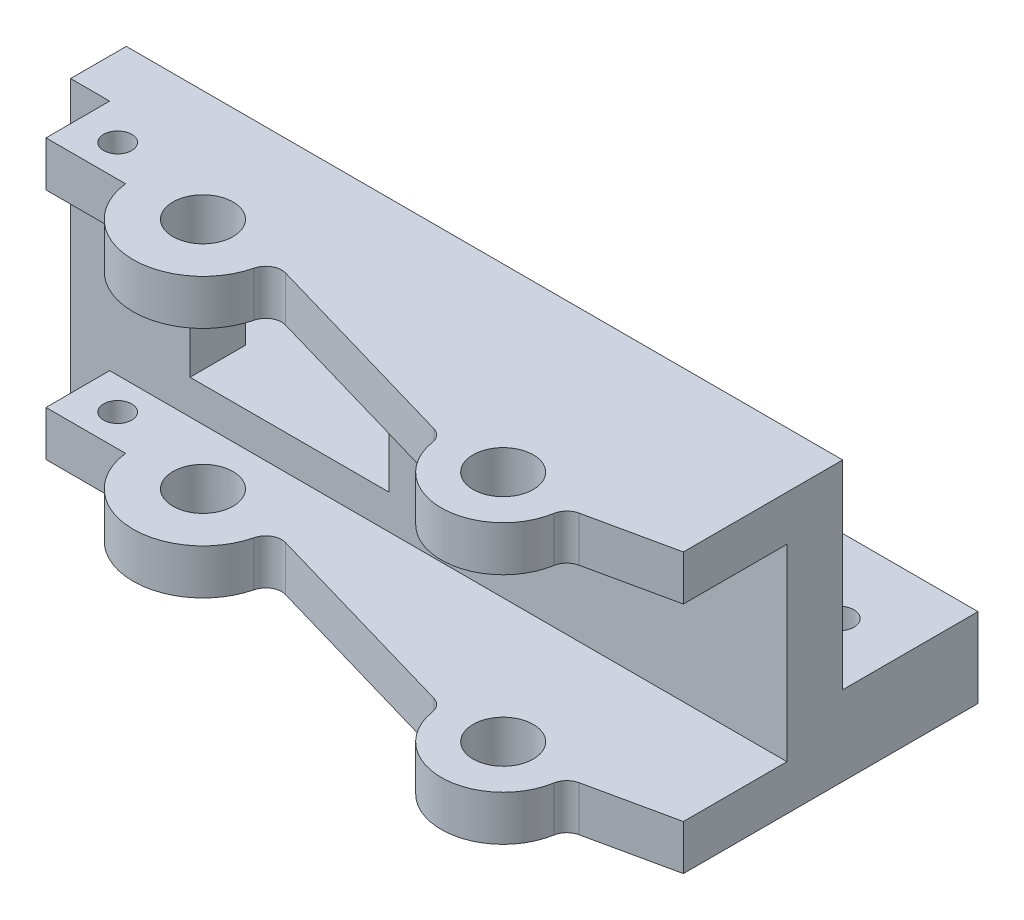
SolidWorks part; units mm, degrees
ref_plane "Front Plane" through (0, 0, 0) normal (0, 0, 1) x (1, 0, 0)
ref_plane "Top Plane" through (0, 0, 0) normal (0, 1, 0) x (1, 0, 0)
ref_plane "Right Plane" through (0, 0, 0) normal (1, 0, 0) x (0, 0, -1)
sketch "Sketch1" plane through (0, 0, 0) normal (0, 0, 1) x (1, 0, 0)
  line L1 (57.15, -22.225) -> (-57.15, -22.225)
  line L2 (57.15, -22.225) -> (57.15, 22.225)
  line L3 (57.15, 22.225) -> (-57.15, 22.225)
  line L4 (-57.15, -22.225) -> (-57.15, 22.225)
  line L5 (57.15, -22.225) -> (-57.15, 22.225) construction
  line L6 (57.15, 22.225) -> (-57.15, -22.225) construction
  point P0 (0, 0)
  dimension "D1" = 44.45
  dimension "D2" = 114.3
extrude "Boss-Extrude1" add sketch "Sketch1" along normal blind 62.23
sketch "Sketch2" plane through (0, 0, 62.23) normal (0, 0, 1) x (1, 0, 0)
  line L0 (-57.15, 22.225) -> (-57.15, -22.225) construction
  line L1 (57.15, -15.025) -> (-57.15, -15.025)
  line L2 (57.15, -15.025) -> (57.15, 15.025)
  line L3 (57.15, 15.025) -> (-57.15, 15.025)
  line L4 (-57.15, -15.025) -> (-57.15, 15.025)
  line L5 (57.15, -15.025) -> (-57.15, 15.025) construction
  line L6 (57.15, 15.025) -> (-57.15, -15.025) construction
  line L7 (57.15, 22.225) -> (-57.15, 22.225) construction
  point P0 (0, 0)
  dimension "D1" = 7.2
extrude "Cut-Extrude2" cut sketch "Sketch2" against normal blind 31.75
sketch "Sketch3" plane through (0, 0, 0) normal (0, 0, -1) x (-1, 0, 0)
  line L0 (-57.15, -22.225) -> (-57.15, 22.225) construction
  line L1 (57.15, 22.225) -> (-57.15, 22.225)
  line L2 (57.15, 22.225) -> (57.15, -9.525)
  line L3 (57.15, -9.525) -> (-57.15, -9.525)
  line L4 (-57.15, 22.225) -> (-57.15, -9.525)
  line L5 (57.15, -22.225) -> (-57.15, -22.225) construction
  dimension "D1" = 12.7
extrude "Cut-Extrude3" cut sketch "Sketch3" against normal blind 21.59
sketch "Sketch5" plane through (0, -22.225, 0) normal (0, -1, 0) x (1, 0, 0)
  line L0 (-3.81, 12.06) -> (46.99, 12.06) construction
  line L1 (57.15, 21.59) -> (-57.15, 21.59) construction
  line L2 (57.15, 62.23) -> (57.15, 0) construction
  circle A0 centre (-3.81, 12.06) radius 2.415
  circle A1 centre (46.99, 12.06) radius 2.415
  dimension "D3" = 4.83
  dimension "D4" = 10.16
  dimension "D1" = 9.53
  dimension "D2" = 50.8
extrude "Cut-Extrude4" cut sketch "Sketch5" against normal blind 25.4
sketch "Sketch7" plane through (0, -22.225, 0) normal (0, -1, 0) x (1, 0, 0)
  line L0 (57.15, 62.23) -> (57.15, 0) construction
  line L1 (-57.15, 0) -> (57.15, 0) construction
  circle A0 centre (31.75, 50.36) radius 4.8
  circle A1 centre (-27.14, 39.37) radius 4.8
  dimension "D1" = 9.6
  dimension "D2" = 25.4
  dimension "D3" = 39.37
  dimension "D4" = 9.6
  dimension "D5" = 58.89
  dimension "D6" = 10.99
extrude "Cut-Extrude6" cut sketch "Sketch7" against normal up to surface (44.45 mm away) up to face at (0, 22.225, 41.91)
sketch "Sketch9" plane through (0, 0, 30.48) normal (0, 0, 1) x (1, 0, 0)
  line L5 (57.15, 15.025) -> (-57.15, 15.025) construction
  line L6 (-38.1, 15.025) -> (-6.35, 15.025)
  line L7 (-38.1, 15.025) -> (-38.1, -15.025)
  line L8 (-38.1, -15.025) -> (-6.35, -15.025)
  line L9 (-6.35, 15.025) -> (-6.35, -15.025)
  line L10 (-57.15, -15.025) -> (57.15, -15.025) construction
  line L11 (-57.15, 15.025) -> (-57.15, -15.025) construction
  line L12 (57.15, -15.025) -> (57.15, 15.025) construction
  dimension "D1" = 63.5
  dimension "25in" = 19.05
extrude "Cut-Extrude7" cut sketch "Sketch9" against normal through all both and the other way through all
sketch "Sketch16" plane through (0, -22.225, 0) normal (0, -1, 0) x (1, 0, 0)
  line L1 (-38.1, 30.48) -> (-57.15, 30.48) construction
  line L4 (-38.2174, 40.64) -> (-38.2174, 30.48)
  line L8 (-57.15, 62.23) -> (57.15, 62.23)
  line L9 (57.15, 62.23) -> (57.15, 47.0103)
  line L10 (57.15, 62.23) -> (57.15, 0) construction
  line L11 (-15.99, 39.37) -> (21.87, 50.36)
  line L12 (41.63, 50.36) -> (57.15, 47.0103)
  line L13 (-49.091, 30.48) -> (-57.15, 30.48)
  line L14 (-38.2174, 30.48) -> (-49.091, 30.48)
  line L15 (-57.15, 30.48) -> (-57.15, 62.23)
  arc A2 (41.63, 50.36) -> (21.87, 50.36) centre (31.75, 50.36) ccw
  arc A3 (-15.99, 39.37) -> (-38.2174, 40.64) centre (-27.14, 39.37) ccw
  circle A4 centre (-27.14, 39.37) radius 4.8 construction
  circle A5 centre (31.75, 50.36) radius 4.8 construction
  point P19 (-36.8467, 44.8566)
  point P20 (-49.091, 30.48)
  dimension "D1" = 6.35
  dimension "D2" = 5.08
  dimension "D3" = 10.16
extrude "Cut-Extrude8" cut sketch "Sketch16" against normal through all
fillet "Fillet1" radius 2.54 6 edges at (21.87, 18.625, 50.36) (41.63, -18.625, 50.36) (41.63, 18.625, 50.36) (-15.99, 18.625, 39.37) (-15.99, -18.625, 39.37) (21.87, -18.625, 50.36)
sketch "Sketch14" plane through (-6.35, 0, 0) normal (-1, 0, 0) x (0, 0, 1)
  line L0 (0, -15.025) -> (30.48, -15.025) construction
  line L1 (21.59, -9.525) -> (0, -9.525)
  line L2 (21.59, -9.525) -> (21.59, -15.025)
  line L3 (21.59, -15.025) -> (0, -15.025)
  line L4 (0, -9.525) -> (0, -15.025)
extrude "Boss-Extrude2" add sketch "Sketch14" along normal up to next
sketch "Sketch17" plane through (0, 0, 21.59) normal (0, 0, 1) x (1, 0, 0)
  line L1 (-6.35, -15.025) -> (-38.1, -15.025)
  line L2 (-6.35, -15.025) -> (-6.35, -9.525)
  line L3 (-6.35, -9.525) -> (-38.1, -9.525)
  line L4 (-38.1, -15.025) -> (-38.1, -9.525)
extrude "Boss-Extrude3" add sketch "Sketch17" along normal up to surface (8.89 mm away) up to face at (25.4, 0, 30.48)
sketch "Sketch25" plane through (-38.2174, 0, 0) normal (-1, 0, 0) x (0, 0, 1)
  line L0 (40.64, 15.025) -> (30.48, 15.025) construction
  line L1 (30.48, 22.225) -> (40.64, 22.225)
  line L2 (30.48, 22.225) -> (30.48, 15.025)
  line L3 (30.48, 15.025) -> (40.64, 15.025)
  line L4 (40.64, 22.225) -> (40.64, 15.025)
  line L5 (39.37, -22.225) -> (50.52, -22.225) construction
  line L6 (30.48, -15.025) -> (40.64, -15.025)
  line L7 (30.48, -15.025) -> (30.48, -22.225)
  line L8 (30.48, -22.225) -> (40.64, -22.225)
  line L9 (40.64, -15.025) -> (40.64, -22.225)
  dimension "D1" = 10.16
extrude "Boss-Extrude5" add sketch "Sketch25" along normal blind 12.7
sketch "Sketch28" plane through (0, -22.225, 0) normal (0, -1, 0) x (-1, 0, 0)
sketch "Sketch30" plane through (0, -22.225, 0) normal (0, -1, 0) x (-1, 0, 0)
  line L0 (50.9174, -40.64) -> (38.2174, -40.64) construction
  line L1 (50.9174, -30.48) -> (50.9174, -40.64) construction
  point P0 (44.5674, -35.56)
  point P5 (44.5674, -40.64)
  point P8 (50.9174, -35.56)
hole_wizard "#8 Clearance Hole1" positions "Sketch30" profile "Sketch29" hole size "#8" standard "ANSI Inch" end condition through all
sketch "Sketch29" plane through (-44.5674, -22.225, 35.56) normal (1, 0, 0) x (0, 0, -1)
  line L0 (0, 0) -> (0, 44.45)
  line L1 (0, 44.45) -> (2.2479, 44.45)
  line L2 (2.2479, 44.45) -> (2.2479, 0)
  line L5 (2.2479, 0) -> (0, 0)
  line L11 (0, -6.35) -> (0, 107.95) construction
  dimension "Thru Hole Dia." = 4.4958
  dimension "Thru Hole Depth" = 44.45
